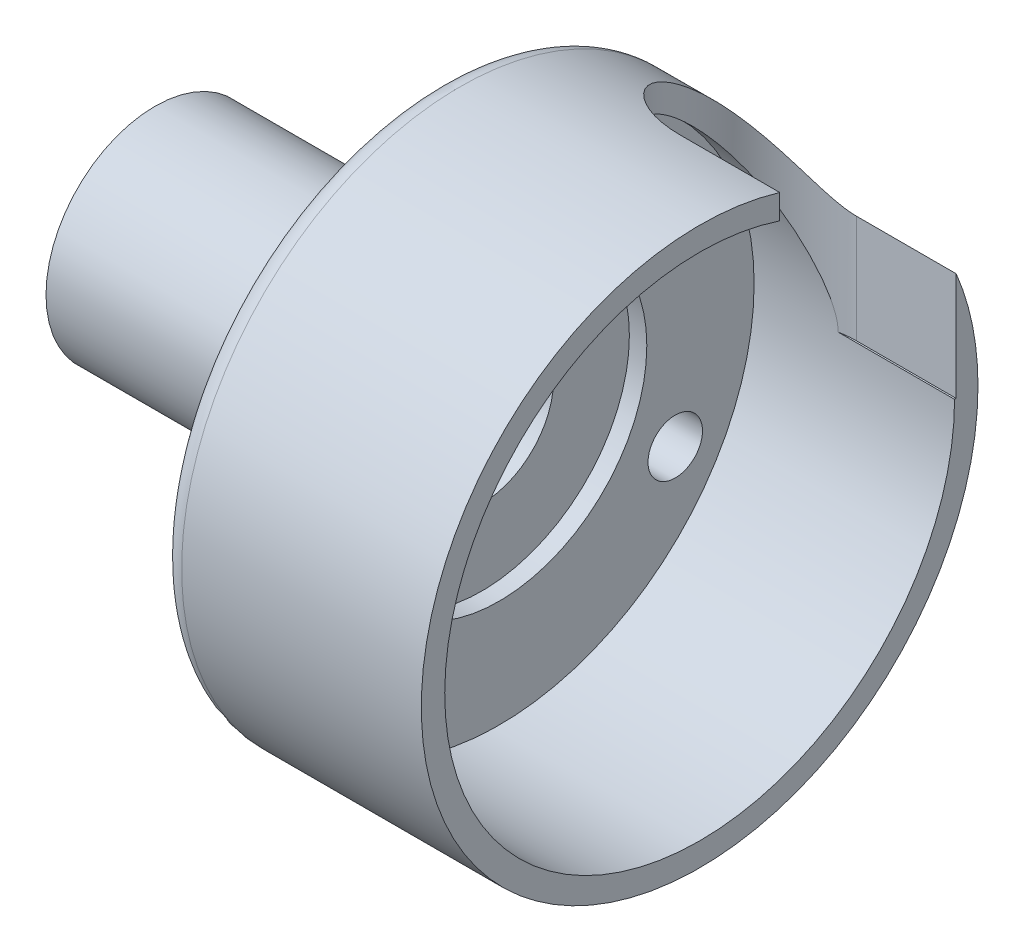
SolidWorks part; units mm, degrees
ref_plane "Front Plane" through (0, 0, 0) normal (0, 0, 1) x (1, 0, 0)
ref_plane "Top Plane" through (0, 0, 0) normal (0, 1, 0) x (1, 0, 0)
ref_plane "Right Plane" through (0, 0, 0) normal (1, 0, 0) x (0, 0, -1)
sketch "Sketch3" plane through (0, 0, 0) normal (1, 0, 0) x (0, 0, -1)
  circle A0 centre (0, 0) radius 5
  circle A1 centre (0, 0) radius 3.3
  dimension "D1" = 10
  dimension "D2" = 6.6
extrude "Boss-Extrude3" add sketch "Sketch3" along normal blind 10 and the other way blind 5 contours A1 | A0 region at (0, 0, 0)
sketch "Sketch10" plane through (10, 0, 0) normal (1, 0, 0) x (0, 0, -1)
  circle A0 centre (0, 0) radius 12.775
  circle A1 centre (0, 0) radius 2.1
  circle A2 centre (0, 0) radius 3.65
  circle M5 centre (0, 0) radius 3.3
  dimension "D1" = 1.55
  dimension "D2" = 4.2
  dimension "D3" = 25.55
extrude "Boss-Extrude5" add sketch "Sketch10" against normal blind 2 contours M5 | A0 region at (10, 0, 3.2067)
sketch "Sketch11" plane through (10, 0, 0) normal (1, 0, 0) x (0, 0, -1)
  circle A0 centre (0, 0) radius 6.775
  circle A1 centre (0, 0) radius 11.275
  circle M2 centre (0, 0) radius 3.3
  dimension "D1" = 13.55
  dimension "D2" = 22.55
extrude "Boss-Extrude6" add sketch "Sketch11" along normal blind 0.8 contours M2 | A0 M2 | A1 region at (10, 0, 6.5834) region at (10, 0, 0)
sketch "Sketch12" plane through (10.8, 0, 0) normal (1, 0, 0) x (0, 0, -1)
  line L1 (0, 9.33) -> (-8.08, -4.665)
  line L2 (-8.08, -4.665) -> (8.08, -4.665)
  line L3 (8.08, -4.665) -> (0, 9.33)
  circle A0 centre (0, 0) radius 4.665 construction
  circle A1 centre (0, 0) radius 11.275 construction
  circle A2 centre (-8.08, -4.665) radius 1.25
  circle A3 centre (8.08, -4.665) radius 1.25
  circle A4 centre (0, 9.33) radius 1.25
  dimension "D2" = 2.5
  dimension "D3" = 2.5
  dimension "D4" = 2.5
  dimension "D1" = 9.33
extrude "Cut-Extrude2" cut sketch "Sketch12" against normal blind 2.75 contours L2 A3 L3 | L3 A4 L1 | L1 A4 L3 | L3 A3 L2 | A2 region at (10.8, 8.5342, 0) region at (10.8, 9.4892, 0) region at (10.8, -4.7446, -8.2178) region at (10.8, -4.2671, -7.3909)
fillet "Fillet3" radius 1 1 edges at (8, 0, -12.775)
sketch "Sketch13" plane through (10, 0, 0) normal (1, 0, 0) x (0, 0, -1)
  circle A0 centre (0, 0) radius 11.275 construction
  circle A1 centre (0, 0) radius 11.275
  circle A2 centre (0, 0) radius 12.775 construction
  circle A3 centre (0, 0) radius 12.775
extrude "Boss-Extrude7" add sketch "Sketch13" along normal blind 10
sketch "Sketch14" plane through (20, 0, 0) normal (1, 0, 0) x (0, 0, -1)
  circle A0 centre (0, 0) radius 11.7
  dimension "D1" = 23.4
extrude "Cut-Extrude3" cut sketch "Sketch14" against normal up to surface (9.2 mm away) up to face at (10.8, 9.33, -1.25)
sketch "Sketch15" plane through (0, 0, 0) normal (0, 1, 0) x (1, 0, 0)
  line L0 (15.4301, 3.675) -> (20, 3.675)
  line L1 (20, -12.775) -> (20, 12.775) construction
  line L2 (15.4301, 11.775) -> (20, 11.775)
  line L3 (20, 11.775) -> (20, 3.675)
  line L4 (20, 12.775) -> (9, 12.775) construction
  line L5 (20, 12.775) -> (9, 12.775)
  arc A0 (15.4301, 11.775) -> (15.4301, 3.675) centre (15.4301, 7.725) ccw
  dimension "D1" = 8.1
  dimension "D2" = 1
extrude "Cut-Extrude5" cut sketch "Sketch15" along normal blind 16 contours L3 L0 A0 L2
sketch "Sketch16" plane through (-5, 0, 0) normal (-1, 0, 0) x (0, 0, 1)
  circle A0 centre (0, 0) radius 4.5
  dimension "D1" = 9
extrude "Cut-Extrude6" cut sketch "Sketch16" against normal blind 14
